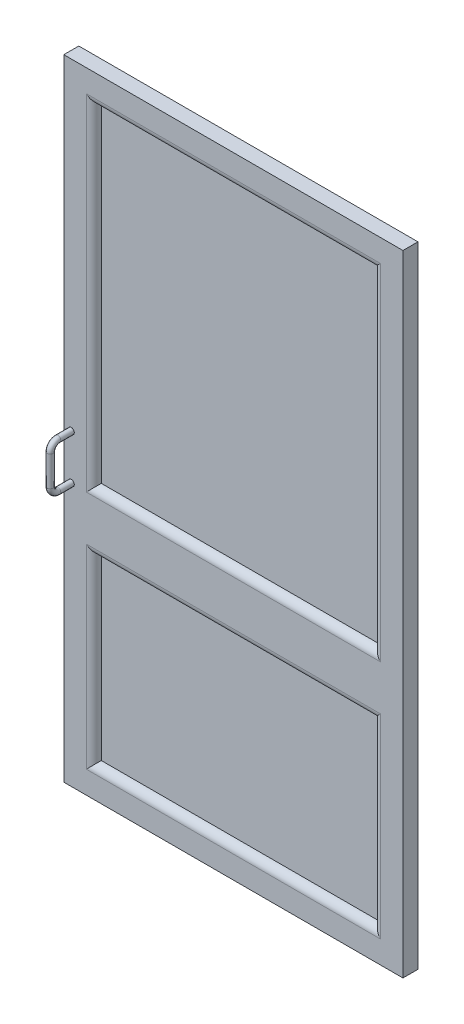
SolidWorks part; units mm, degrees
material "Teak"
ref_plane "Front Plane" through (0, 0, 0) normal (0, 0, 1) x (1, 0, 0)
ref_plane "Top Plane" through (0, 0, 0) normal (0, 1, 0) x (1, 0, 0)
ref_plane "Right Plane" through (0, 0, 0) normal (1, 0, 0) x (0, 0, -1)
sketch "Sketch1" plane through (0, 0, 0) normal (0, 0, 1) x (1, 0, 0)
  line L1 (0, 0) -> (1130.4283, 0)
  line L2 (0, 0) -> (0, 2100)
  line L3 (0, 2100) -> (1130.4283, 2100)
  line L4 (1130.4283, 0) -> (1130.4283, 2100)
  dimension "D1" = 2100
  dimension "D2" = 1130.4283
extrude "Boss-Extrude1" add sketch "Sketch1" along normal blind 50
sketch "Sketch3" plane through (0, 0, 50) normal (0, 0, 1) x (1, 0, 0)
  line L0 (0, 0) -> (1130.4283, 0) construction
  line L1 (100, 700) -> (1030.4283, 700)
  line L2 (100, 700) -> (100, 100)
  line L3 (100, 100) -> (1030.4283, 100)
  line L4 (1030.4283, 700) -> (1030.4283, 100)
  line L5 (100, 2000) -> (1030.4283, 2000)
  line L6 (100, 2000) -> (100, 900)
  line L7 (100, 900) -> (1030.4283, 900)
  line L8 (1030.4283, 2000) -> (1030.4283, 900)
  line L9 (0, 2100) -> (0, 0) construction
  line L10 (1130.4283, 0) -> (1130.4283, 2100) construction
  line L11 (1130.4283, 2100) -> (0, 2100) construction
  dimension "D1" = 100
  dimension "D2" = 100
  dimension "D3" = 100
  dimension "D4" = 200
  dimension "D5" = 600
  dimension "D6" = 100
extrude "Cut-Extrude1" cut sketch "Sketch3" against normal blind 25
fillet "Fillet1" radius 25 8 edges at (565.2142, 100, 50) (100, 400, 50) (1030.4283, 400, 50) (565.2142, 700, 50) (100, 1450, 50) (565.2142, 900, 50) (1030.4283, 1450, 50) (565.2142, 2000, 50)
ref_plane "Plane1" through (25, 0, 0) normal (-1, 0, 0) x (0, 0, 1)
sketch "Sketch4" plane through (25, 0, 0) normal (-1, 0, 0) x (0, 0, 1)
  line L0 (50, 1026.3855) -> (95, 1026.3855)
  line L1 (50, 2100) -> (50, 0) construction
  line L2 (120, 1001.3855) -> (120, 901.3855)
  line L3 (95, 876.3855) -> (48.3698, 876.3855)
  arc A0 (120, 1001.3855) -> (95, 1026.3855) centre (95, 1001.3855) ccw
  arc A1 (120, 901.3855) -> (95, 876.3855) centre (95, 901.3855) cw
  dimension "D3" = 25
  dimension "D1" = 70
  dimension "D2" = 150
sketch "Sketch5" plane through (0, 0, 50) normal (0, 0, 1) x (1, 0, 0)
  line L0 (25, 1026.3855) -> (25, 1001.3855) construction
  line L1 (25, 27.5) -> (25, -27.5) construction
  circle A0 centre (25, 1026.3855) radius 10
  dimension "D1" = 20
sweep "Sweep1" add profiles "Sketch5" path "Sketch4"
ref_plane "Plane2" through (0, 0, 25) normal (0, 0, 1) x (1, 0, 0)
ref_plane "Plane3" through (1130.4283, 2100, 50) normal (-1, 0, 0) x (0, 0, 1)
sketch "Sketch7" plane through (1130.4283, 2100, 50) normal (-1, 0, 0) x (0, 0, 1)
scale "Scale2" scale about origin uniform scaling yes scale factor 0.25
scale "Scale3" scale about origin uniform scaling yes scale factor 0.32
